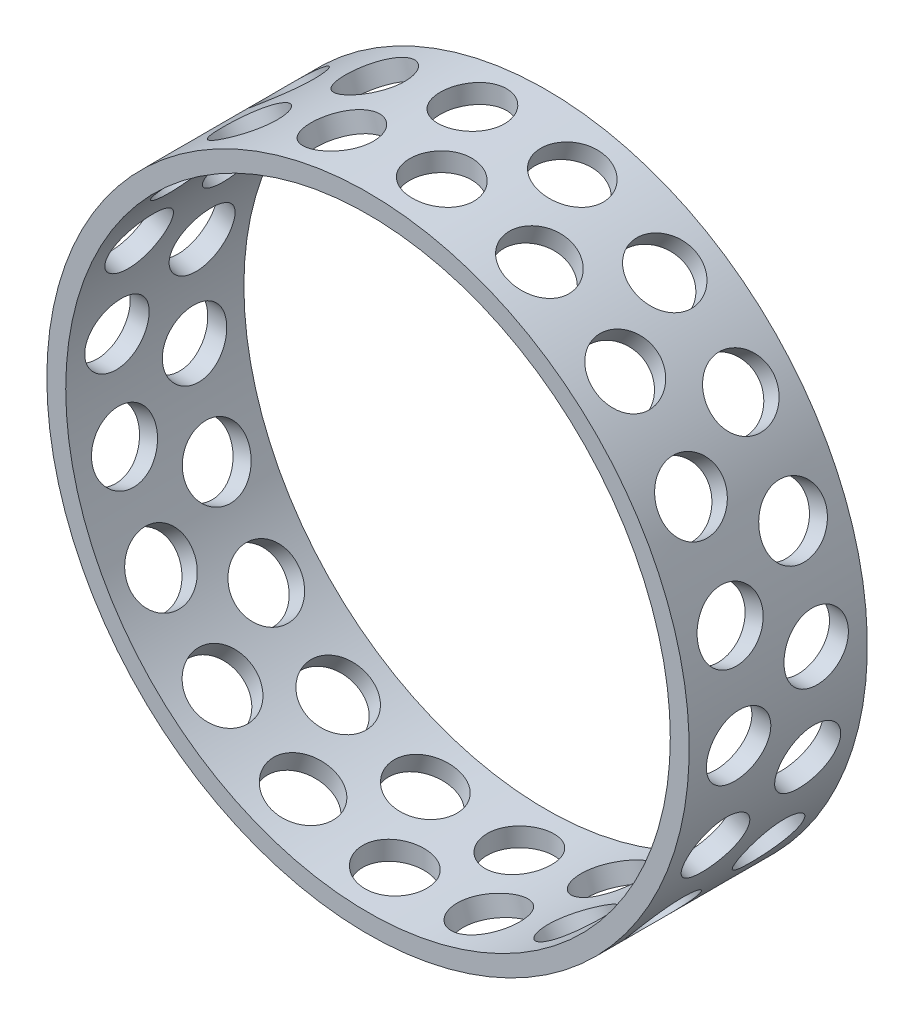
SolidWorks part; units mm, degrees
material "Plain Carbon Steel"
ref_plane "Front Plane" through (0, 0, 0) normal (0, 0, 1) x (1, 0, 0)
ref_plane "Top Plane" through (0, 0, 0) normal (0, 1, 0) x (1, 0, 0)
ref_plane "Right Plane" through (0, 0, 0) normal (1, 0, 0) x (0, 0, -1)
sketch "Sketch1" plane through (0, 0, 0) normal (1, 0, 0) x (0, 0, -1)
  line L0 (1, 84.9998) -> (48.15, 84.9998)
  line L1 (48.15, 84.9998) -> (48.15, 79.9998)
  line L2 (48.15, 79.9998) -> (1, 79.9998)
  line L3 (1, 79.9998) -> (1, 84.9998)
  dimension "D1" = 84.9998
  dimension "D2" = 5
  dimension "D3" = 47.15
  dimension "D4" = 1
ref_axis "Axis1" through (0, 0, -50.5075) along (0, 0, 1)
revolve "Revolve1" add sketch "Sketch1" angle 360 about axis through (0, 0, -50.5075) along (0, 0, 1)
sketch "Sketch2" plane through (0, 0, 0) normal (1, 0, 0) x (0, 0, -1)
  line L0 (14.3098, 6.2149) -> (24.575, 0) construction
  line L1 (50.5075, 0) -> (-1.3575, 0) construction
  line L2 (24.575, 0) -> (34.8402, -6.2149) construction
  line L3 (1, 84.9998) -> (1, -84.9998) construction
  circle A0 centre (14.3098, 6.2149) radius 8.5
  circle A1 centre (34.8402, -6.2149) radius 8.5
  dimension "D1" = 17
  dimension "D2" = 12
  dimension "D3" = 23.575
extrude "Cut-Extrude1" cut sketch "Sketch2" against normal through all
pattern_circular "CirPattern1" count 20 over 360 about axis through (0, 0, -50.5075) along (0, 0, 1) of "Cut-Extrude1"
equation "\"TubeDiameter\" = 6.6929in"
equation "\"D1@Sketch1\"=\"TubeDiameter\"/2"
